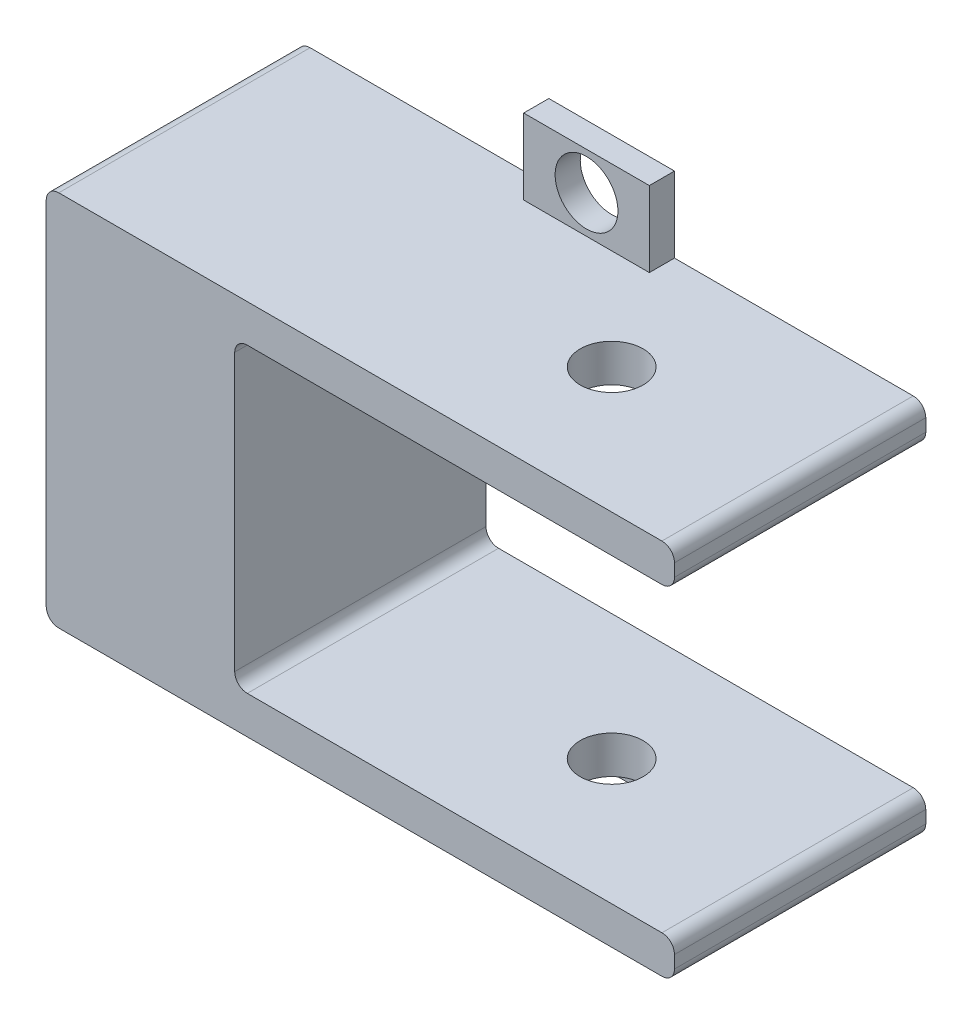
SolidWorks part; units mm, degrees
ref_plane "Front Plane" through (0, 0, 0) normal (0, 0, 1) x (1, 0, 0)
ref_plane "Top Plane" through (0, 0, 0) normal (0, 1, 0) x (1, 0, 0)
ref_plane "Right Plane" through (0, 0, 0) normal (1, 0, 0) x (0, 0, -1)
sketch "Sketch1" plane through (0, 0, 0) normal (0, 0, 1) x (1, 0, 0)
  line L1 (0, 0) -> (63.5, 0)
  line L2 (0, 0) -> (0, 38.1)
  line L3 (0, 38.1) -> (63.5, 38.1)
  line L4 (63.5, 0) -> (63.5, 38.1)
  dimension "D1" = 38.1
  dimension "D2" = 63.5
extrude "Boss-Extrude1" add sketch "Sketch1" along normal blind 25.4
sketch "Sketch3" plane through (0, 0, 0) normal (0, 0, -1) x (-1, 0, 0)
  line L0 (-63.5, 0) -> (-63.5, 38.1) construction
  line L1 (-63.5, 34.29) -> (-19.05, 34.29)
  line L2 (-63.5, 34.29) -> (-63.5, 3.81)
  line L3 (-63.5, 3.81) -> (-19.05, 3.81)
  line L4 (-19.05, 34.29) -> (-19.05, 3.81)
  line L9 (0, 0) -> (-63.5, 0) construction
  line L10 (-63.5, 38.1) -> (0, 38.1) construction
  dimension "D1" = 3.81
  dimension "D2" = 3.81
  dimension "D3" = 44.45
extrude "Cut-Extrude1" cut sketch "Sketch3" against normal blind 38.1
sketch "Sketch5" plane through (0, 0, 0) normal (0, -1, 0) x (1, 0, 0)
  line L0 (0, 0) -> (63.5, 0) construction
  circle A0 centre (44.45, 12.7) radius 3.175
  dimension "D1" = 6.35
  dimension "D2" = 12.7
  dimension "D3" = 19.05
extrude "Cut-Extrude2" cut sketch "Sketch5" against normal blind 76.2
fillet "Fillet3" radius 1.27 8 edges at (0, 38.1, 12.7) (0, 0, 12.7) (19.05, 3.81, 12.7) (19.05, 34.29, 12.7) (63.5, 3.81, 12.7) (63.5, 38.1, 12.7) (63.5, 34.29, 12.7) (63.5, 0, 12.7)
sketch "Sketch6" plane through (0, 38.1, 0) normal (0, 1, 0) x (1, 0, 0)
  line L5 (1.27, -25.4) -> (62.23, -25.4) construction
  line L6 (1.27, -22.86) -> (25.4, -22.86) construction
  line L7 (25.4, -25.4) -> (38.1, -25.4)
  line L8 (25.4, -25.4) -> (25.4, -22.86)
  line L9 (25.4, -22.86) -> (38.1, -22.86)
  line L10 (38.1, -25.4) -> (38.1, -22.86)
  line L11 (1.27, 0) -> (1.27, -25.4) construction
  line L12 (1.27, 0) -> (62.23, 0) construction
  dimension "D1" = 2.54
  dimension "D2" = 12.7
  dimension "D3" = 24.13
  dimension "D4" = 60.96
sketch "Sketch7" plane through (0, 0, 0) normal (0, -1, 0) x (1, 0, 0)
  line L0 (62.23, 22.86) -> (38.1, 22.86) construction
  line L1 (62.23, 0) -> (62.23, 25.4) construction
  line L2 (1.27, 25.4) -> (62.23, 25.4) construction
  line L3 (38.1, 22.86) -> (25.4, 22.86)
  line L4 (38.1, 22.86) -> (38.1, 25.4)
  line L5 (38.1, 25.4) -> (25.4, 25.4)
  line L6 (25.4, 22.86) -> (25.4, 25.4)
  dimension "D1" = 24.13
  dimension "D2" = 12.7
  dimension "D3" = 2.54
sketch "Sketch10" plane through (0, 0, 0) normal (0, -1, 0) x (1, 0, 0)
  line L0 (62.23, 2.54) -> (38.1, 2.54) construction
  line L1 (62.23, 0) -> (62.23, 25.4) construction
  line L2 (1.27, 0) -> (62.23, 0) construction
  line L3 (38.1, 2.54) -> (25.4, 2.54)
  line L4 (38.1, 2.54) -> (38.1, 0)
  line L5 (38.1, 0) -> (25.4, 0)
  line L6 (25.4, 2.54) -> (25.4, 0)
  dimension "D1" = 24.13
  dimension "D2" = 12.7
  dimension "D3" = 2.54
extrude "Boss-Extrude4" add sketch "Sketch10" along normal blind 7.62
sketch "Sketch11" plane through (0, 38.1, 0) normal (0, 1, 0) x (1, 0, 0)
  line L0 (1.27, -2.54) -> (25.4, -2.54) construction
  line L1 (1.27, 0) -> (1.27, -25.4) construction
  line L2 (62.23, 0) -> (1.27, 0) construction
  line L3 (25.4, -2.54) -> (38.1, -2.54)
  line L4 (25.4, -2.54) -> (25.4, 0)
  line L5 (25.4, 0) -> (38.1, 0)
  line L6 (38.1, -2.54) -> (38.1, 0)
  dimension "D1" = 24.13
  dimension "D2" = 12.7
  dimension "D3" = 2.54
extrude "Boss-Extrude5" add sketch "Sketch11" along normal blind 7.62
sketch "Sketch12" plane through (0, 0, 2.54) normal (0, 0, 1) x (1, 0, 0)
  line L0 (25.4, 41.91) -> (38.1, 41.91) construction
  line L1 (25.4, 45.72) -> (25.4, 38.1) construction
  line L2 (38.1, 45.72) -> (38.1, 38.1) construction
  line L3 (25.4, -3.81) -> (38.1, -3.81) construction
  line L4 (25.4, -7.62) -> (25.4, 0) construction
  line L5 (38.1, -7.62) -> (38.1, 0) construction
  circle A0 centre (31.75, 41.91) radius 3.175
  circle A1 centre (31.75, -3.81) radius 3.175
  dimension "D1" = 6.35
  dimension "D2" = 6.35
extrude "Cut-Extrude5" cut sketch "Sketch12" against normal up to next
sketch "Sketch13" plane through (0, 0, 0) normal (0, 0, -1) x (-1, 0, 0)
  line L0 (-19.05, 19.05) -> (0, 19.05) construction
  line L1 (-19.05, 5.08) -> (-19.05, 33.02) construction
  line L2 (0, 36.83) -> (0, 1.27) construction
  line L3 (-9.525, 38.1) -> (-9.525, 0) construction
  line L4 (-1.27, 38.1) -> (-62.23, 38.1) construction
  line L5 (-1.27, 0) -> (-25.4, 0) construction
  line L7 (-12.065, 21.59) -> (-6.985, 21.59)
  line L8 (-12.065, 21.59) -> (-12.065, 16.51)
  line L9 (-12.065, 16.51) -> (-6.985, 16.51)
  line L10 (-6.985, 21.59) -> (-6.985, 16.51)
  line L11 (-12.065, 21.59) -> (-6.985, 16.51) construction
  line L12 (-12.065, 16.51) -> (-6.985, 21.59) construction
  point P12 (-9.525, 19.05)
  dimension "D1" = 5.08
  dimension "D2" = 5.08
extrude "Boss-Extrude6" add sketch "Sketch13" along normal blind 6.35
sketch "Sketch14" plane through (12.065, 0, 0) normal (1, 0, 0) x (0, 0, -1)
  line L0 (6.35, 21.59) -> (0, 21.59) construction
  line L1 (6.35, 16.51) -> (3.81, 16.51)
  line L2 (6.35, 16.51) -> (6.35, 21.59)
  line L3 (6.35, 21.59) -> (3.81, 21.59)
  line L4 (3.81, 16.51) -> (3.81, 21.59)
  dimension "D1" = 2.54
sketch "Sketch15" plane through (12.065, 0, 0) normal (1, 0, 0) x (0, 0, -1)
  line L0 (3.175, 16.51) -> (3.175, 21.59) construction
  line L1 (6.35, 16.51) -> (0, 16.51) construction
  line L2 (6.35, 21.59) -> (0, 21.59) construction
  circle A0 centre (3.175, 19.05) radius 1.905
  dimension "D1" = 3.81
extrude "Cut-Extrude6" cut sketch "Sketch15" against normal up to next
fillet "Fillet5" radius 2.54 2 edges at (9.525, 21.59, -6.35) (9.525, 16.51, -6.35)
